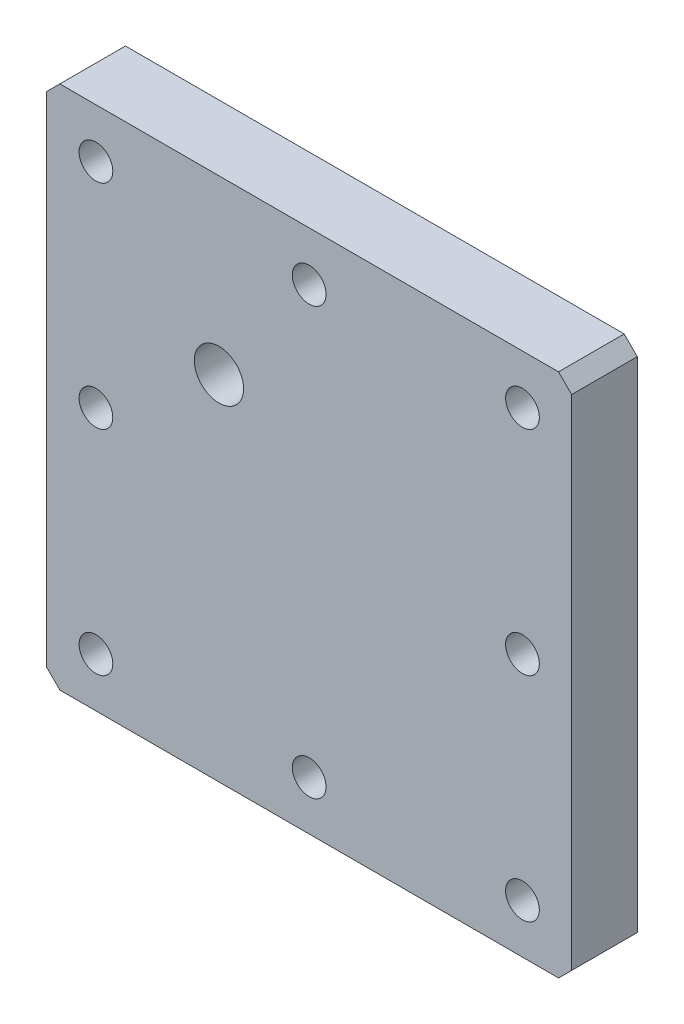
SolidWorks part; units mm, degrees
ref_plane "Front Plane" through (0, 0, 0) normal (0, 0, 1) x (1, 0, 0)
ref_plane "Top Plane" through (0, 0, 0) normal (0, 1, 0) x (1, 0, 0)
ref_plane "Right Plane" through (0, 0, 0) normal (1, 0, 0) x (0, 0, -1)
sketch "Sketch1" plane through (0, 0, 0) normal (0, 0, 1) x (1, 0, 0)
  line L0 (-50.8, 48.26) -> (-48.26, 50.8)
  line L1 (-48.26, -50.8) -> (48.26, -50.8)
  line L2 (-50.8, -48.26) -> (-50.8, 48.26)
  line L3 (-48.26, 50.8) -> (48.26, 50.8)
  line L4 (50.8, -48.26) -> (50.8, 48.26)
  line L5 (-50.8, -50.8) -> (50.8, 50.8) construction
  line L6 (-50.8, 50.8) -> (50.8, -50.8) construction
  line L7 (48.26, 50.8) -> (50.8, 48.26)
  line L8 (48.26, -50.8) -> (50.8, -48.26)
  line L9 (-50.8, -48.26) -> (-48.26, -50.8)
  line L10 (-41.275, 41.275) -> (0, 41.275)
  line L11 (41.275, -41.275) -> (-41.275, -41.275) construction
  line L12 (41.275, -41.275) -> (41.275, 41.275) construction
  line L13 (41.275, 41.275) -> (-41.275, 41.275) construction
  line L14 (-41.275, -41.275) -> (-41.275, 41.275) construction
  line L15 (41.275, -41.275) -> (-41.275, 41.275) construction
  line L16 (41.275, 41.275) -> (-41.275, -41.275) construction
  line L17 (41.275, -41.275) -> (0, -41.275)
  line L18 (-34.925, 34.925) -> (0, 0)
  line L19 (-34.925, -34.925) -> (34.925, -34.925)
  line L20 (-34.925, -34.925) -> (-34.925, 34.925)
  line L21 (-34.925, 34.925) -> (34.925, 34.925)
  line L22 (34.925, -34.925) -> (34.925, 34.925)
  line L23 (-34.925, -34.925) -> (34.925, 34.925) construction
  line L24 (-34.925, 34.925) -> (34.925, -34.925) construction
  line L25 (-17.4625, 17.4625) -> (-50.8, 17.4625) construction
  line L26 (-17.4625, 17.4625) -> (-17.4625, 50.8) construction
  circle A0 centre (-41.275, 41.275) radius 3.2639
  circle A1 centre (0, 41.275) radius 3.2639
  circle A2 centre (41.275, 41.275) radius 3.2639
  circle A3 centre (41.275, 0) radius 3.2639
  circle A4 centre (41.275, -41.275) radius 3.2639
  circle A5 centre (0, -41.275) radius 3.2639
  circle A6 centre (-41.275, -41.275) radius 3.2639
  circle A7 centre (-41.275, 0) radius 3.2639
  circle A10 centre (-17.4625, 17.4625) radius 4.7625
  point P0 (0, 0)
  point P14 (0, 0)
  point P35 (0, 0)
  dimension "D5" = 6.5278
  dimension "D6" = 69.85
  dimension "D8" = 9.525
  dimension "D1" = 101.6
  dimension "D2" = 101.6
  dimension "D3" = 82.55
  dimension "D4" = 82.55
  dimension "D7" = 69.85
  dimension "D13" = 33.3375
extrude "Boss-Extrude1" add sketch "Sketch1" along normal blind 12.7 contours L19 L22 L21 L20 | L2 L9 L1 L8 L4 L7 L3 L0 A4 A5 A1 A0 A7 A6 A3 A2 L22 L19 L20 L21 region at (-48.514, 48.514, 0) region at (0.2588, -0.2588, 0)
